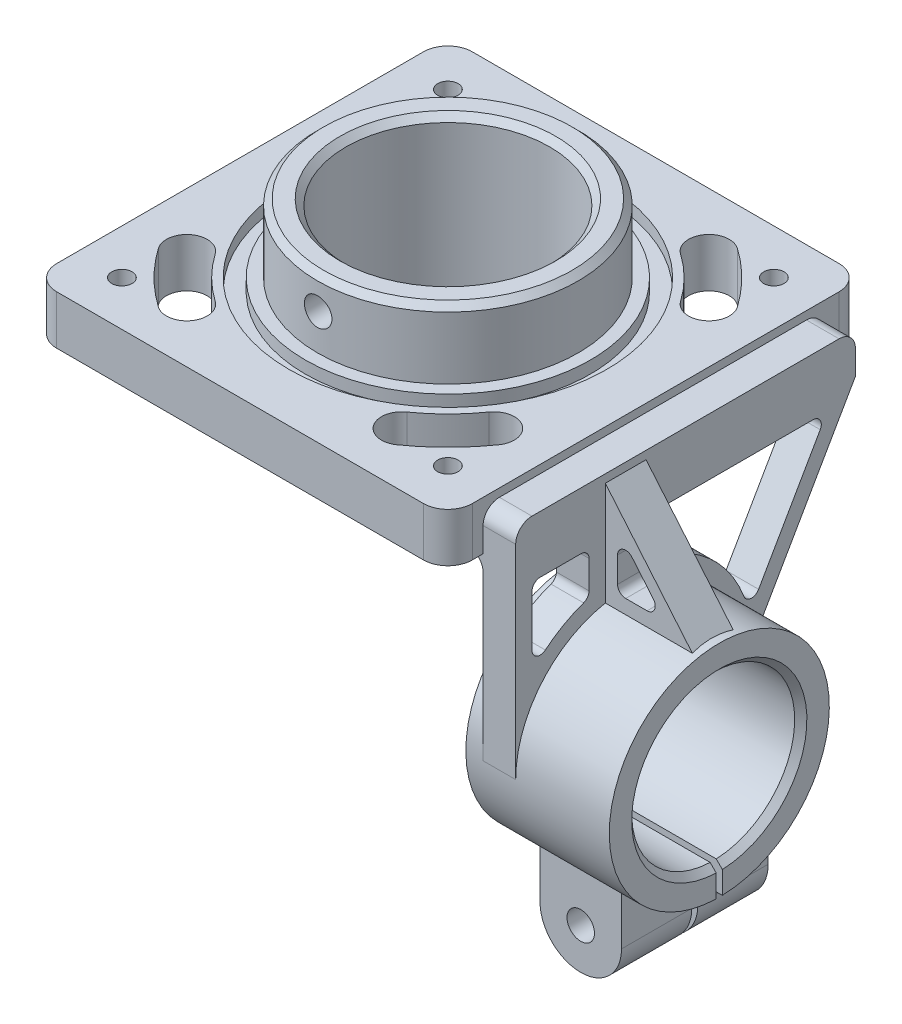
SolidWorks part; units mm, degrees
ref_plane "Face" through (0, 0, 0) normal (0, 0, 1) x (1, 0, 0)
ref_plane "Dessus" through (0, 0, 0) normal (0, 1, 0) x (1, 0, 0)
ref_plane "Droite" through (0, 0, 0) normal (1, 0, 0) x (0, 0, -1)
sketch "Esquisse1" plane through (0, 0, 0) normal (0, 1, 0) x (1, 0, 0)
  line L0 (-59.8186, 41.8854) -> (0, 0) construction
  line L1 (-80.9625, -80.9625) -> (80.9625, -80.9625)
  line L2 (-80.9625, -80.9625) -> (-80.9625, 80.9625)
  line L3 (-80.9625, 80.9625) -> (80.9625, 80.9625)
  line L4 (80.9625, -80.9625) -> (80.9625, 80.9625)
  line L5 (-80.9625, -80.9625) -> (80.9625, 80.9625) construction
  line L6 (-80.9625, 80.9625) -> (80.9625, -80.9625) construction
  line L7 (0, 0) -> (-41.8854, 59.8186) construction
  circle A0 centre (0, 0) radius 39.6875
  arc A1 (-41.8854, 59.8186) -> (-59.8186, 41.8854) centre (0, 0) ccw construction
  arc A2 (-46.4382, 66.3206) -> (-66.3206, 46.4382) centre (0, 0) ccw
  arc A3 (-37.3327, 53.3166) -> (-53.3166, 37.3327) centre (0, 0) ccw
  arc A4 (-37.3327, 53.3166) -> (-46.4382, 66.3206) centre (-41.8854, 59.8186) ccw
  arc A5 (-66.3206, 46.4382) -> (-53.3166, 37.3327) centre (-59.8186, 41.8854) ccw
  arc A6 (59.8186, 41.8854) -> (41.8854, 59.8186) centre (0, 0) ccw construction
  arc A7 (66.3206, 46.4382) -> (46.4382, 66.3206) centre (0, 0) ccw
  arc A8 (53.3166, 37.3327) -> (37.3327, 53.3166) centre (0, 0) ccw
  arc A9 (53.3166, 37.3327) -> (66.3206, 46.4382) centre (59.8186, 41.8854) ccw
  arc A10 (46.4382, 66.3206) -> (37.3327, 53.3166) centre (41.8854, 59.8186) ccw
  arc A11 (41.8854, -59.8186) -> (59.8186, -41.8854) centre (0, 0) ccw construction
  arc A12 (46.4382, -66.3206) -> (66.3206, -46.4382) centre (0, 0) ccw
  arc A13 (37.3327, -53.3166) -> (53.3166, -37.3327) centre (0, 0) ccw
  arc A14 (37.3327, -53.3166) -> (46.4382, -66.3206) centre (41.8854, -59.8186) ccw
  arc A15 (66.3206, -46.4382) -> (53.3166, -37.3327) centre (59.8186, -41.8854) ccw
  arc A16 (-59.8186, -41.8854) -> (-41.8854, -59.8186) centre (0, 0) ccw construction
  arc A17 (-66.3206, -46.4382) -> (-46.4382, -66.3206) centre (0, 0) ccw
  arc A18 (-53.3166, -37.3327) -> (-37.3327, -53.3166) centre (0, 0) ccw
  arc A19 (-53.3166, -37.3327) -> (-66.3206, -46.4382) centre (-59.8186, -41.8854) ccw
  arc A20 (-46.4382, -66.3206) -> (-37.3327, -53.3166) centre (-41.8854, -59.8186) ccw
  point P0 (0, 0)
  point P10 (-51.6365, 51.6365)
  point P23 (51.6365, 51.6365)
  point P30 (51.6365, -51.6365)
  point P37 (-51.6365, -51.6365)
  point P42 (0, 0)
  dimension "D3" = 79.375
  dimension "D6" = 7.9375
  dimension "D1" = 161.925
  dimension "D2" = 161.925
  dimension "D4" = 73.025
  dimension "D5" = 20
  dimension "D7" = 4
extrude "Boss.-Extru.1" add sketch "Esquisse1" against normal blind 19.05
hole_wizard "Trou taraudé 3/8-161" positions "Esquisse2" profile "Esquisse3" tap size "3/8-16" standard "Ansi Inch" end condition through all
sketch "Esquisse2" plane through (0, 0, 0) normal (0, 1, 0) x (1, 0, 0)
  line L0 (80.9625, 80.9625) -> (-80.9625, 80.9625) construction
  line L1 (-80.9625, 80.9625) -> (-80.9625, -80.9625) construction
  point P0 (-63.5, 63.5)
  point P2 (63.5, 63.5)
  point P5 (-63.5, -63.5)
  point P7 (63.5, -63.5)
  dimension "D1" = 127
  dimension "D2" = 127
  dimension "D3" = 17.4625
  dimension "D4" = 17.4625
sketch "Esquisse3" plane through (-63.5, 0, -63.5) normal (1, 0, 0) x (0, 0, 1)
  line L0 (0, 0) -> (0, 19.05)
  line L1 (0, 19.05) -> (3.9687, 19.05)
  line L2 (3.9687, 19.05) -> (3.9687, 0)
  line L5 (3.9687, 0) -> (0, 0)
  line L11 (0, -6.35) -> (0, 107.95) construction
  dimension "Diamètre du trou pour taraudage jusqu'au prochain" = 7.9375
  dimension "Profondeur du trou pour taraudage jusqu'au prochain" = 19.05
cosmetic thread "Filetage de perçage1" parameters "D2"=9.525
cosmetic thread "Filetage de perçage2" parameters "D2"=9.525
cosmetic thread "Filetage de perçage3" parameters "D2"=9.525
cosmetic thread "Filetage de perçage4" parameters "D2"=9.525
sketch "Esquisse4" plane through (0, 0, 0) normal (0, 1, 0) x (1, 0, 0)
  circle A0 centre (0, 0) radius 55.5625
  circle A1 centre (0, 0) radius 61.9125
  dimension "D1" = 111.125
  dimension "D2" = 123.825
extrude "Enlèv. mat.-Extru.1" cut sketch "Esquisse4" against normal blind 4.7625 contours A1 | A0
sketch "Esquisse5" plane through (0, 0, 0) normal (0, 1, 0) x (1, 0, 0)
  circle A0 centre (0, 0) radius 50.8
  circle A1 centre (0, 0) radius 39.6875
  dimension "D1" = 101.6
  dimension "D2" = 79.375
extrude "Boss.-Extru.2" add sketch "Esquisse5" along normal blind 26.67
chamfer "Chanfrein1" [suppressed] distance 2.3813 angle 45
fillet "Congé1" radius 9.525 4 edges at (-80.9625, -9.525, -80.9625) (80.9625, -9.525, -80.9625) (-80.9625, -9.525, 80.9625) (80.9625, -9.525, 80.9625)
ref_plane "Plan1" through (0, 0, 50.8) normal (0, 0, 1) x (1, 0, 0)
hole_wizard "Trou taraudé 1/2-131" positions "Esquisse9" profile "Esquisse10" tap size "1/2-13" standard "Ansi Inch" end condition up to next
sketch "Esquisse9" plane through (0, 0, 50.8) normal (0, 0, 1) x (1, 0, 0)
  line L0 (50.8, 26.67) -> (-50.8, 26.67) construction
  point P0 (0, 13.97)
  dimension "D1" = 12.7
sketch "Esquisse10" plane through (0, 13.97, 50.8) normal (1, 0, 0) x (0, -1, 0)
  line L0 (0, 0) -> (0, 11.1125)
  line L1 (0, 11.1125) -> (5.3581, 11.1125)
  line L2 (5.3581, 11.1125) -> (5.3581, 0)
  line L5 (5.3581, 0) -> (0, 0)
  line L11 (0, -6.35) -> (0, 107.95) construction
  dimension "Diamètre du trou pour taraudage jusqu'au prochain" = 10.7163
  dimension "Profondeur du trou pour taraudage jusqu'au prochain" = 11.1125
cosmetic thread "Filetage de perçage5" parameters "D2"=12.7
chamfer "Chanfrein2" distance 2.3813 angle 45 2 edges at (0, 26.67, 39.6875) (0, 26.67, 50.8)
sketch "Esquisse11" plane through (0, -19.05, 0) normal (0, -1, 0) x (-1, 0, 0)
  circle A0 centre (0, 0) radius 53.975
  circle A2 centre (0, 0) radius 39.6875
  dimension "D1" = 107.95
  dimension "D2" = 79.375
extrude "Boss.-Extru.3" add sketch "Esquisse11" along normal blind 19.05
chamfer "Chanfrein4" distance 2.3813 angle 45 1 edges at (0, -38.1, -39.6875)
sketch "Esquisse13" plane through (80.9625, 0, 0) normal (1, 0, 0) x (0, 0, -1)
  line L0 (-53.975, -38.1) -> (53.975, -38.1) construction
  line L1 (-67.2465, -88.9) -> (-67.2465, -3.175)
  line L2 (-67.2465, -3.175) -> (65.0875, -3.175)
  line L3 (65.0875, -3.175) -> (65.0875, -19.05)
  line L4 (65.0875, -19.05) -> (12.7976, -110.2242)
  line L5 (-71.4375, 0) -> (71.4375, 0) construction
  line L6 (80.9625, 0) -> (80.9625, -19.05) construction
  line L7 (-71.4375, -19.05) -> (71.4375, -19.05) construction
  arc A0 (-67.2465, -88.9) -> (12.7976, -110.2242) centre (-24.384, -88.9) ccw
  circle A1 centre (-24.384, -88.9) radius 31.75
  dimension "D1" = 85.725
  dimension "D2" = 63.5
  dimension "D3" = 24.384
  dimension "D4" = 50.8
  dimension "D5" = 3.175
  dimension "D6" = 15.875
extrude "Boss.-Extru.4" add sketch "Esquisse13" along normal blind 12.7
fillet "Congé2" radius 6.35 2 edges at (87.3125, -3.175, -65.0875) (87.3125, -3.175, 67.2465)
sketch "Esquisse15" plane through (93.6625, 0, 0) normal (1, 0, 0) x (0, 0, -1)
  line L0 (-24.384, -57.15) -> (-24.384, -120.65) construction
  line L1 (-56.134, -88.9) -> (7.366, -88.9) construction
  circle A0 centre (-24.384, -88.9) radius 31.75 construction
  circle A1 centre (-24.384, -88.9) radius 42.8625
  circle A2 centre (-24.384, -88.9) radius 31.75
  dimension "D1" = 85.725
fillet "Congé3" radius 6.35 1 edges at (80.9625, -19.05, 1.0795)
ref_plane "Plan2" through (74.2442, 0, 0) normal (1, 0, 0) x (0, 0, -1)
sketch "Esquisse18" plane through (80.9625, 0, 0) normal (-1, 0, 0) x (0, 0, 1)
  circle A0 centre (24.384, -88.9) radius 42.8625
  circle A1 centre (24.384, -88.9) radius 31.75
  dimension "D1" = 85.725
  dimension "D2" = 63.5
extrude "Boss.-Extru.6" add sketch "Esquisse18" along normal up to surface (6.7183 mm away) up to plane "Plan2"
sketch "Esquisse19" plane through (93.6625, 0, 0) normal (1, 0, 0) x (0, 0, -1)
  line L0 (-24.384, -57.15) -> (-24.384, -120.65) construction
  line L1 (-56.134, -88.9) -> (7.366, -88.9) construction
  circle A1 centre (-24.384, -88.9) radius 31.75 construction
  circle A2 centre (-24.384, -88.9) radius 42.8625
  circle A3 centre (-24.384, -88.9) radius 31.75
  dimension "D1" = 85.725
  dimension "D2" = 63.5
extrude "Boss.-Extru.7" add sketch "Esquisse19" along normal blind 36.4617
sketch "Esquisse20" plane through (93.6625, 0, 0) normal (1, 0, 0) x (0, 0, -1)
  line L3 (-10.0965, -39.5086) -> (-10.0965, -28.575)
  line L4 (-6.9215, -25.4) -> (48.6444, -25.4)
  line L5 (-24.384, -57.15) -> (-24.384, -120.65) construction
  line L6 (-56.134, -88.9) -> (7.366, -88.9) construction
  line L7 (-60.8965, -48.4888) -> (-60.8965, -28.575)
  line L8 (-57.7215, -25.4) -> (-41.8465, -25.4)
  line L9 (-38.6715, -28.575) -> (-38.6715, -39.5086)
  line L10 (-67.2465, -9.525) -> (-67.2465, -88.9) construction
  line L11 (-80.9625, -19.05) -> (-71.4375, -19.05) construction
  line L12 (51.3986, -30.1546) -> (27.3939, -72.01)
  line L14 (12.7976, -110.2242) -> (65.0875, -19.05) construction
  arc A7 (-55.701, -50.938) -> (-40.7882, -42.502) centre (-24.384, -88.9) cw
  circle A8 centre (-24.384, -88.9) radius 31.75 construction
  arc A9 (21.6686, -71.5498) -> (-7.9798, -42.502) centre (-24.384, -88.9) ccw
  arc A10 (48.6444, -25.4) -> (51.3986, -30.1546) centre (48.6444, -28.575) cw
  arc A11 (21.6686, -71.5498) -> (27.3939, -72.01) centre (24.6397, -70.4304) ccw
  arc A12 (-7.9798, -42.502) -> (-10.0965, -39.5086) centre (-6.9215, -39.5086) cw
  arc A13 (-10.0965, -28.575) -> (-6.9215, -25.4) centre (-6.9215, -28.575) cw
  arc A14 (-41.8465, -25.4) -> (-38.6715, -28.575) centre (-41.8465, -28.575) cw
  arc A15 (-40.7882, -42.502) -> (-38.6715, -39.5086) centre (-41.8465, -39.5086) ccw
  arc A16 (-55.701, -50.938) -> (-60.8965, -48.4888) centre (-57.7215, -48.4888) cw
  arc A17 (-60.8965, -28.575) -> (-57.7215, -25.4) centre (-57.7215, -28.575) cw
  dimension "D1" = 49.2125
  dimension "D5" = 63.5
  dimension "D7" = 49.2125
  dimension "D9" = 3.175
  dimension "D2" = 6.35
  dimension "D3" = 6.35
  dimension "D4" = 38.6715
  dimension "D6" = 63.5
  dimension "D8" = 6.35
extrude "Enlèv. mat.-Extru.2" cut sketch "Esquisse20" against normal up to next
ref_plane "Plan3" through (0, 0, 24.384) normal (0, 0, 1) x (1, 0, 0)
sketch "Esquisse22" plane through (0, 0, 24.384) normal (0, 0, 1) x (1, 0, 0)
  line L0 (93.6625, -6.368) -> (126.9492, -46.0375)
  line L1 (130.1242, -131.7625) -> (130.1242, -46.0375) construction
  line L2 (93.6625, -9.525) -> (93.6625, -88.9) construction
  line L4 (130.1242, -46.0375) -> (93.6625, -46.0375) construction
  dimension "D1" = 3.175
  dimension "D2" = 50
rib "Nervure3" sketch "Esquisse22" sketch "Esquisse22" thickness 15.875 extrusion direction parallel to sketch draft on no parameters "D1"=15.875
sketch "Esquisse23" plane through (0, 0, 32.3215) normal (0, 0, 1) x (1, 0, 0)
  line L0 (98.425, -38.1) -> (98.425, -28.1761)
  line L1 (104.0322, -26.1352) -> (112.3594, -36.0591)
  line L2 (109.9272, -41.275) -> (101.6, -41.275)
  line L3 (93.6625, -6.368) -> (93.6625, -46.7789) construction
  line L4 (93.6625, -6.368) -> (127.5713, -46.7789) construction
  line L5 (130.1242, -46.0375) -> (126.9492, -46.0375) construction
  arc A0 (112.3594, -36.0591) -> (109.9272, -41.275) centre (109.9272, -38.1) cw
  arc A1 (98.425, -38.1) -> (101.6, -41.275) centre (101.6, -38.1) ccw
  arc A2 (98.425, -28.1761) -> (104.0322, -26.1352) centre (101.6, -28.1761) cw
  dimension "D4" = 3.175
  dimension "D1" = 4.7625
  dimension "D2" = 4.7625
  dimension "D3" = 4.7625
extrude "Enlèv. mat.-Extru.3" cut sketch "Esquisse23" against normal through all
ref_plane "Plan4" through (0, 0, 52.959) normal (0, 0, 1) x (1, 0, 0)
sketch "Esquisse25" plane through (0, 0, 52.959) normal (0, 0, 1) x (1, 0, 0)
  line L0 (120.5992, -107.6734) -> (88.8492, -107.6734)
  line L1 (88.8492, -107.6734) -> (88.8492, -139.7)
  line L2 (120.5992, -139.7) -> (120.5992, -107.6734)
  line L3 (74.2442, -46.0375) -> (74.2442, -131.7625) construction
  line L4 (88.8492, -139.7) -> (120.5992, -139.7) construction
  line L5 (74.2442, -88.9) -> (130.1242, -88.9) construction
  line L6 (130.1242, -131.7625) -> (130.1242, -46.0375) construction
  arc A0 (88.8492, -139.7) -> (120.5992, -139.7) centre (104.7242, -139.7) ccw
  point P5 (104.7242, -107.6734)
  dimension "D1" = 15.875
  dimension "D2" = 30.48
  dimension "D3" = 50.8
  dimension "D4" = 18.7734
extrude "Boss.-Extru.8" add sketch "Esquisse25" against normal blind 57.15
sketch "Esquisse26" plane through (120.5992, 0, 0) normal (1, 0, 0) x (0, 0, -1)
  line L0 (-49.9891, -107.6734) -> (1.2211, -107.6734)
  arc A0 (-49.9891, -107.6734) -> (1.2211, -107.6734) centre (-24.384, -88.9) ccw
  arc A1 (-49.9891, -107.6734) -> (1.2211, -107.6734) centre (-24.384, -88.9) ccw construction
extrude "Enlèv. mat.-Extru.4" cut sketch "Esquisse26" against normal blind 57.15
sketch "Esquisse27" plane through (130.1242, 0, 0) normal (1, 0, 0) x (0, 0, -1)
  line L1 (-25.5746, -110.4662) -> (-23.1934, -110.4662)
  line L2 (-25.5746, -110.4662) -> (-25.5746, -162.3471)
  line L3 (-25.5746, -162.3471) -> (-23.1934, -162.3471)
  line L7 (-23.1934, -110.4662) -> (-23.1934, -162.3471)
  line L8 (-52.959, -139.7) -> (-52.959, -120.8478) construction
  circle A0 centre (-24.384, -88.9) radius 31.75 construction
  dimension "D1" = 27.3844
  dimension "D2" = 2.3813
  dimension "D3" = 21.5662
  dimension "D4" = 51.8809
extrude "Enlèv. mat.-Extru.5" cut sketch "Esquisse27" against normal through all
hole_wizard "Trou taraudé 1/2-132" positions "Esquisse28" profile "Esquisse29" tap size "1/2-13" standard "Ansi Inch" end condition up to next
sketch "Esquisse28" plane through (0, 0, 52.959) normal (0, 0, 1) x (1, 0, 0)
  line L2 (130.1242, -46.0375) -> (130.1242, -131.7625) construction
  line L3 (74.2442, -46.0375) -> (74.2442, -131.746) construction
  point P0 (104.7242, -139.7)
  point P14 (130.1242, -88.9)
  dimension "D1" = 85.725
  dimension "D2" = 50.8
  dimension "D3" = 30.48
sketch "Esquisse29" plane through (104.7242, -139.7, 52.959) normal (1, 0, 0) x (0, -1, 0)
  line L0 (0, 0) -> (0, 27.3844)
  line L1 (0, 27.3844) -> (5.3581, 27.3844)
  line L2 (5.3581, 27.3844) -> (5.3581, 0)
  line L5 (5.3581, 0) -> (0, 0)
  line L11 (0, -6.35) -> (0, 107.95) construction
  dimension "Diamètre du trou pour taraudage jusqu'au prochain" = 10.7163
  dimension "Profondeur du trou pour taraudage jusqu'au prochain" = 27.3844
cosmetic thread "Filetage de perçage6" parameters "D2"=12.7
chamfer "Chanfrein5" distance 2.3813 angle 45 2 edges at (74.2442, -57.15, 24.384) (130.1242, -57.15, 24.384)
hole_wizard "Chambrage pour vis à tête ronde bombée 1/21" positions "Esquisse30" profile "Esquisse31" counterbore size "1/2" standard "Ansi Inch" end condition up to next
sketch "Esquisse30" plane through (0, 0, -4.191) normal (0, 0, -1) x (-1, 0, 0)
  line L0 (-130.1242, -46.0375) -> (-130.1242, -131.7625) construction
  line L1 (-74.2442, -131.746) -> (-74.2442, -46.0375) construction
  point P0 (-104.7242, -139.7)
  point P12 (-130.1242, -88.9)
  dimension "D1" = 85.725
  dimension "D2" = 30.48
  dimension "D3" = 50.8
sketch "Esquisse31" plane through (104.7242, -139.7, -4.191) normal (1, 0, 0) x (0, 1, 0)
  line L0 (0, 0) -> (0, 27.3844)
  line L1 (0, 27.3844) -> (6.7469, 27.3844)
  line L3 (6.7469, 27.3844) -> (6.7469, 12.7)
  line L4 (6.7469, 12.7) -> (10.3187, 12.7)
  line L5 (10.3187, 12.7) -> (10.3187, 0)
  line L7 (10.3187, 0) -> (0, 0)
  line L11 (0, -6.35) -> (0, 107.95) construction
  dimension "Diamètre du perçage jusqu'au prochain" = 13.4937
  dimension "Profondeur du perçage jusqu'au prochain" = 27.3844
  dimension "Diamètre du chambrage" = 20.6375
  dimension "Profondeur du chambrage" = 12.7
